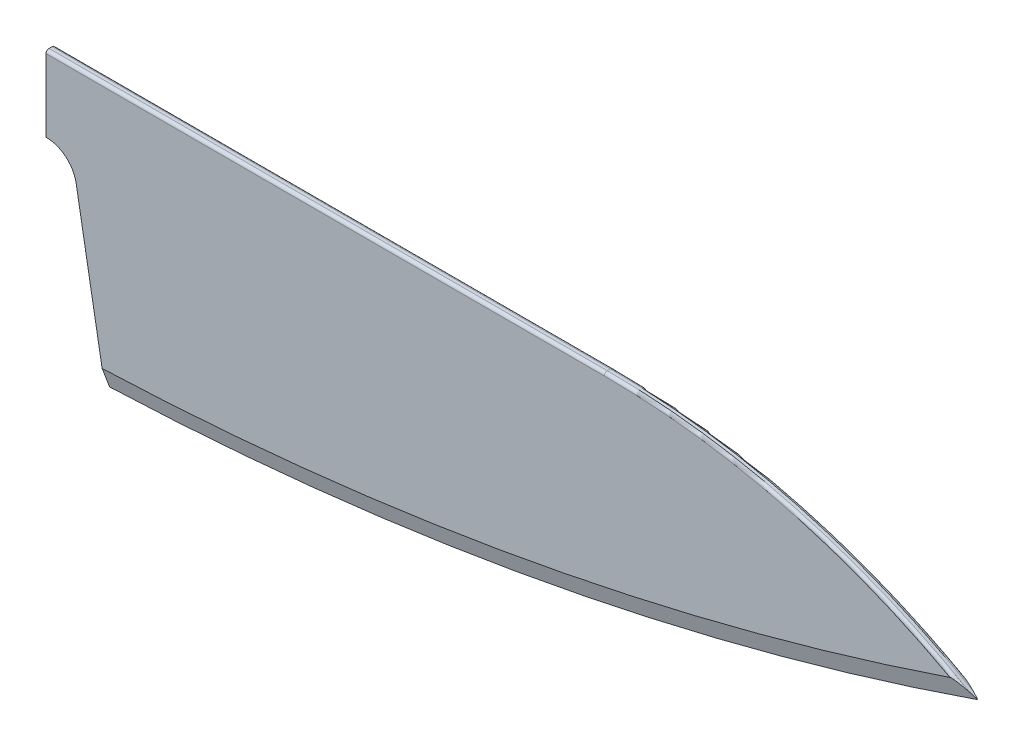
SolidWorks part; units mm, degrees
material "Commercially Pure CP-Ti UNS R50700  Grade 4 (SS)"
ref_plane "Front Plane" through (0, 0, 0) normal (0, 0, 1) x (1, 0, 0)
ref_plane "Top Plane" through (0, 0, 0) normal (0, 1, 0) x (1, 0, 0)
ref_plane "Right Plane" through (0, 0, 0) normal (1, 0, 0) x (0, 0, -1)
sketch "Sketch1" plane through (0, 0, 0) normal (0, 0, 1) x (1, 0, 0)
  line L0 (180, -10) -> (365, -10)
  line L1 (180, -10) -> (180, -35)
  line L2 (180, -35) -> (180.1477, -35)
  line L3 (189.9958, -43.2635) -> (200, -100)
  arc A0 (365, -10) -> (490, -45.122) centre (365, -250) cw
  arc A1 (180.1477, -35) -> (189.9958, -43.2635) centre (180.1477, -45) cw
  arc A2 (200, -100) -> (490, -45.122) centre (161.1011, 899.2432) ccw
  dimension "D4" = 10
  dimension "D9" = 240
  dimension "D10" = 1000
  dimension "D1" = 25
  dimension "D2" = 180
  dimension "D3" = 100
  dimension "D5" = 90
  dimension "D6" = 290
  dimension "D7" = 185
  dimension "D8" = 310
  dimension "D11" = 10
extrude "Boss-Extrude1" add sketch "Sketch1" along normal mid plane 3
chamfer "Chamfer1" distance 8 angle 15 2 edges at (347.0358, -83.319, -1.5) (347.0358, -83.319, 1.5) first distance on face at (255.8719, -39.8196, -1.5) first distance on face at (255.8719, -39.8196, 1.5)
fillet "Fillet1" radius 1 4 edges at (424.8119, -17.5725, -1.5) (424.8119, -17.5725, 1.5) (272.5, -10, -1.5) (272.5, -10, 1.5)
